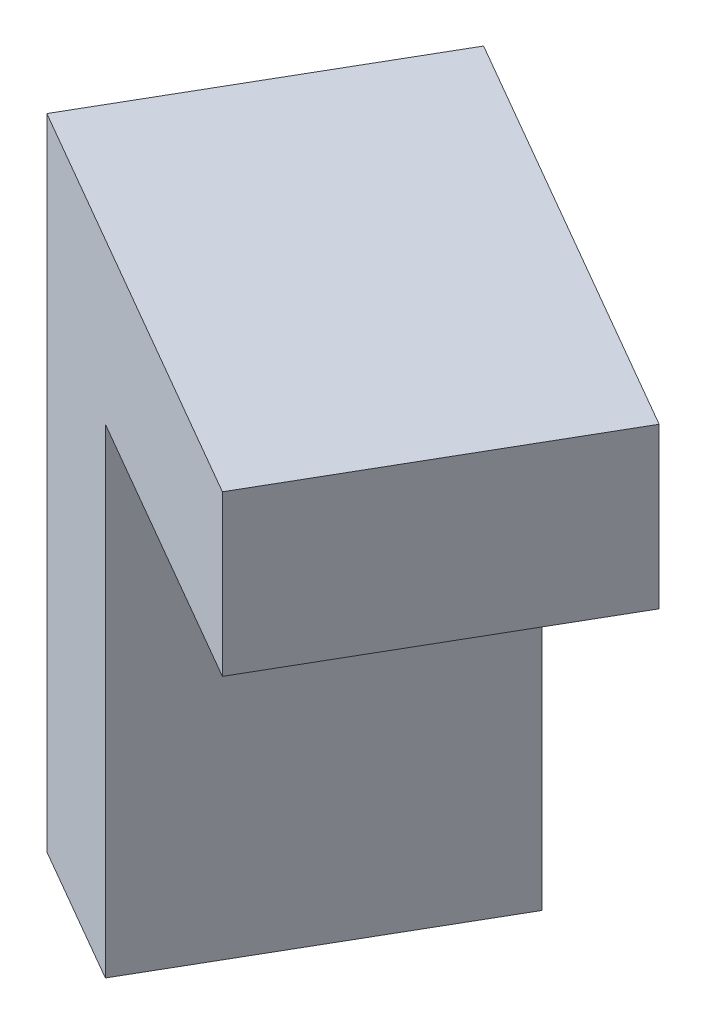
SolidWorks part; units mm, degrees
ref_plane "Front Plane" through (0, 0, 0) normal (0, 0, 1) x (1, 0, 0)
ref_plane "Top Plane" through (0, 0, 0) normal (0, 1, 0) x (1, 0, 0)
ref_plane "Right Plane" through (0, 0, 0) normal (1, 0, 0) x (0, 0, -1)
ref_axis "Axis1" through (0, -4, 0) along (0, -1, 0)
ref_plane "Plane1" through (0, 0, 0) normal (-0.5, 0, 0.866) x (0, -1, 0)
ref_plane "Plane2" through (-7.5, 0, 12.9904) normal (-0.5, 0, 0.866) x (0, -1, 0)
sketch "Sketch1" plane through (-7.5, 0, 12.9904) normal (-0.5, 0, 0.866) x (0, -1, 0)
  line L0 (5, 5) -> (25, 5)
  line L1 (25, 5) -> (25, 10)
  line L2 (25, 10) -> (10, 10)
  line L3 (10, 10) -> (10, 20)
  line L4 (10, 20) -> (5, 20)
  line L5 (5, 20) -> (5, 5)
extrude "Boss-Extrude1" add sketch "Sketch1" along normal blind 10
